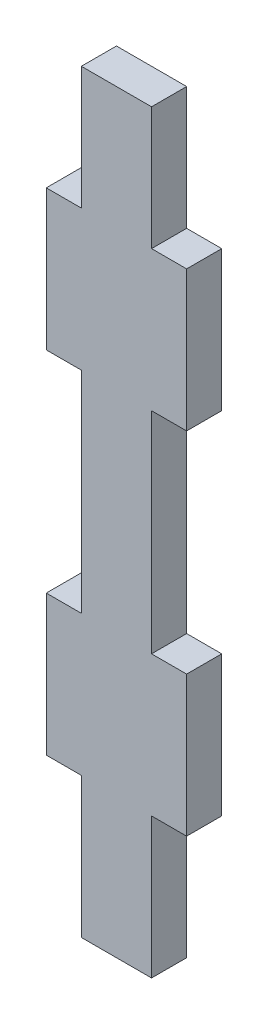
SolidWorks part; units mm, degrees
ref_plane "Front Plane" through (0, 0, 0) normal (0, 0, 1) x (1, 0, 0)
ref_plane "Top Plane" through (0, 0, 0) normal (0, 1, 0) x (1, 0, 0)
ref_plane "Right Plane" through (0, 0, 0) normal (1, 0, 0) x (0, 0, -1)
sketch "Sketch1" plane through (0, 0, 0) normal (0, 0, 1) x (1, 0, 0)
  line L1 (12.7, -7.9375) -> (0, -7.9375)
  line L2 (12.7, -7.9375) -> (12.7, -144.4625)
  line L3 (12.7, -144.4625) -> (0, -144.4625)
  line L4 (0, -7.9375) -> (0, -144.4625)
extrude "Boss-Extrude1" add sketch "Sketch1" along normal blind 6.35
sketch "Sketch2" plane through (0, 0, 0) normal (-1, 0, 0) x (0, 0, 1)
  line L0 (0, -7.9375) -> (0, -144.4625) construction
  line L1 (0, -119.0625) -> (6.35, -119.0625)
  line L2 (0, -119.0625) -> (0, -93.6625)
  line L3 (0, -93.6625) -> (6.35, -93.6625)
  line L4 (6.35, -119.0625) -> (6.35, -93.6625)
  line L5 (6.35, -7.9375) -> (6.35, -144.4625) construction
  dimension "D1" = 25.4
  dimension "D2" = 25.4
extrude "Boss-Extrude2" add sketch "Sketch2" along normal blind 6.35
pattern_linear "LPattern1" count 2 spacing 63.5 along (0, 1, 0) of "Boss-Extrude2"
sketch "Sketch3" plane through (12.7, 0, 0) normal (1, 0, 0) x (0, 0, -1)
  line L0 (-6.35, -144.4625) -> (-6.35, -7.9375) construction
  line L1 (-6.35, -119.0625) -> (0, -119.0625)
  line L2 (-6.35, -119.0625) -> (-6.35, -93.6625)
  line L3 (-6.35, -93.6625) -> (0, -93.6625)
  line L4 (0, -119.0625) -> (0, -93.6625)
  line L5 (0, -144.4625) -> (0, -7.9375) construction
  dimension "D1" = 25.4
  dimension "D2" = 25.4
extrude "Boss-Extrude3" add sketch "Sketch3" along normal blind 6.35
pattern_linear "LPattern2" count 2 spacing 63.5 along (0, 1, 0) of "Boss-Extrude3"
